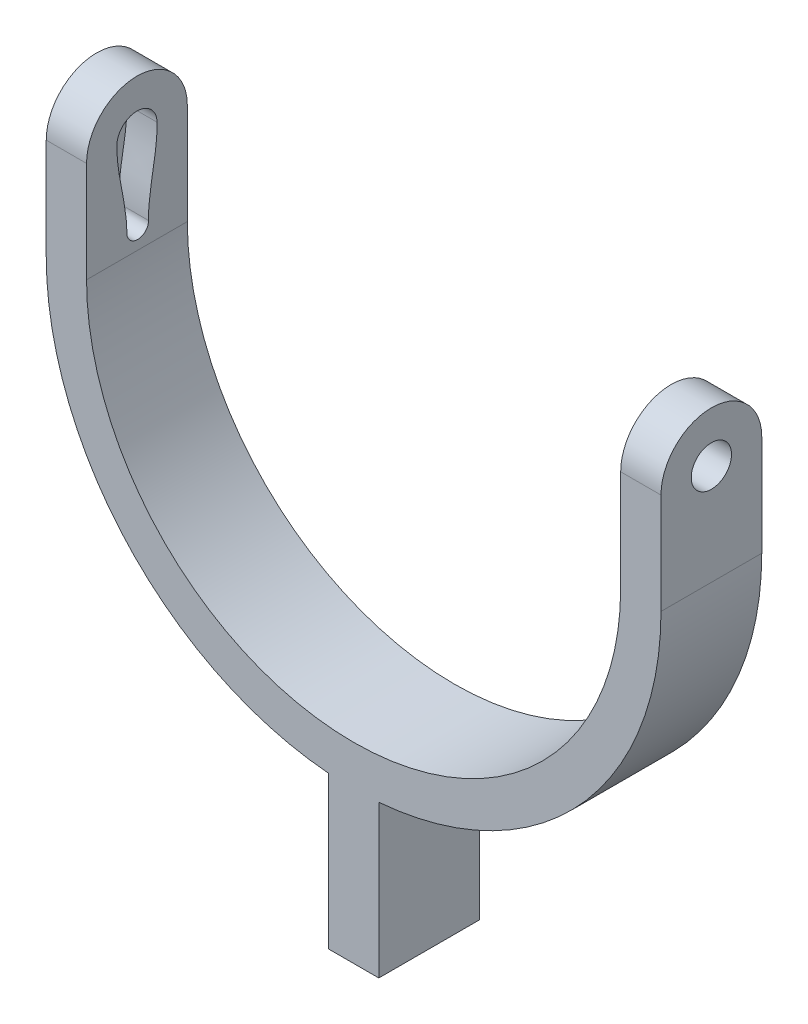
SolidWorks part; units mm, degrees
ref_plane "Front" through (0, 0, 0) normal (0, 0, 1) x (1, 0, 0)
ref_plane "Top" through (0, 0, 0) normal (0, 1, 0) x (1, 0, 0)
ref_plane "Right" through (0, 0, 0) normal (1, 0, 0) x (0, 0, -1)
sketch "Sketch2" plane through (0, 0, 0) normal (0, 0, 1) x (1, 0, 0)
  line L0 (0, 0) -> (0, 39770.9139) construction
  line L1 (0, 0) -> (39770.9139, 0) construction
  line L2 (-26.5, 0) -> (-26.5, 10)
  line L3 (26.5, 0) -> (26.5, 10)
  line L4 (-30.5, 0) -> (-30.5, 10)
  line L5 (30.5, 0) -> (30.5, 10)
  line L6 (26.5, 10) -> (30.5, 10)
  line L7 (-30.5, 10) -> (-26.5, 10)
  line L8 (-2.5, -30.3974) -> (-2.5, -45.5)
  line L9 (-2.5, -45.5) -> (2.5, -45.5)
  line L10 (2.5, -45.5) -> (2.5, -30.3974)
  arc A0 (-26.5, 0) -> (26.5, 0) centre (0, 0) ccw
  arc A1 (-30.5, 0) -> (30.5, 0) centre (0, 0) ccw
  point P17 (0, -30.5)
  dimension "D1" = 53
  dimension "D2" = 10
  dimension "D4" = 5
  dimension "D5" = 15
  dimension "D3" = 4
extrude "Boss-Extrude1" add sketch "Sketch2" along normal blind 10 contours L4 A1 L5 L6 L3 A0 L2 L7 | A1 L8 L9 L10 region at (0, -27.2322, 0) region at (0, -37.9829, 0)
sketch "Sketch3" plane through (30.5, 0, 0) normal (1, 0, 0) x (0, 0, -1)
  line L0 (-10, 10) -> (0, 10) construction
  circle A1 centre (-5, 10) radius 2
  circle A2 centre (-5, 10) radius 5
  line M3 (0, 10) -> (-10, 10)
  dimension "D1" = 4
  dimension "D2" = 10
extrude "Boss-Extrude2" add sketch "Sketch3" against normal up to surface (4 mm away) up to face at (26.5, 5, 5)
extrude "Boss-Extrude3" add sketch "Sketch3<2>" against normal up to surface (61 mm away) from surface up to face at (-30.5, 5, 5) starting at face at (-26.5, 5, 5)
sketch "Sketch3<2>" plane through (30.5, 0, 0) normal (1, 0, 0) x (0, 0, -1) same geometry as "Sketch3"
extrude "Cut-Extrude1" cut sketch "Sketch3<3>" against normal through all both and the other way through all contours A1 M3 region at (30.5, 9.1512, 5)
sketch "Sketch3<3>" plane through (30.5, 0, 0) normal (1, 0, 0) x (0, 0, -1) same geometry as "Sketch3"
sketch "Sketch4" plane through (-30.5, 0, 0) normal (-1, 0, 0) x (0, 0, 1)
  line L0 (3, 10) -> (4.9251, 2) construction
  line L1 (4.9251, 2) -> (7, 10) construction
  line L2 (4.9986, 9.8485) -> (-462.9159, -49987.962) construction
  circle A0 centre (5, 10) radius 2 construction
  arc A1 (6.7479, 9.028) -> (3.219, 9.0901) centre (5, 10) ccw
  circle A2 centre (4.9251, 2) radius 1.0749
  spline S0 degree 3 poles (7, 10) (7, 8.7184) (6.5384, 6.0748) (6, 3.4222) (6, 2) knots 0 0 0 0 0.472302 1 1 1 1
  spline S1 degree 3 poles (3.0004, 10.0374) (2.9764, 8.756) (3.3884, 6.1042) (3.8771, 3.442) (3.8504, 2.0201) knots 0 0 0 0 0.472302 1 1 1 1
  circle M2 centre (5, 10) radius 2
  dimension "D1" = 8
extrude "Cut-Extrude2" cut sketch "Sketch4" along normal blind 3 from surface contours S1 A2 S0 A1 M2 | A2 region at (-30.5, 5.9185, 4.9618) region at (-30.5, 2, 4.9251) starting at face at (-26.5, 6.25, 5)
